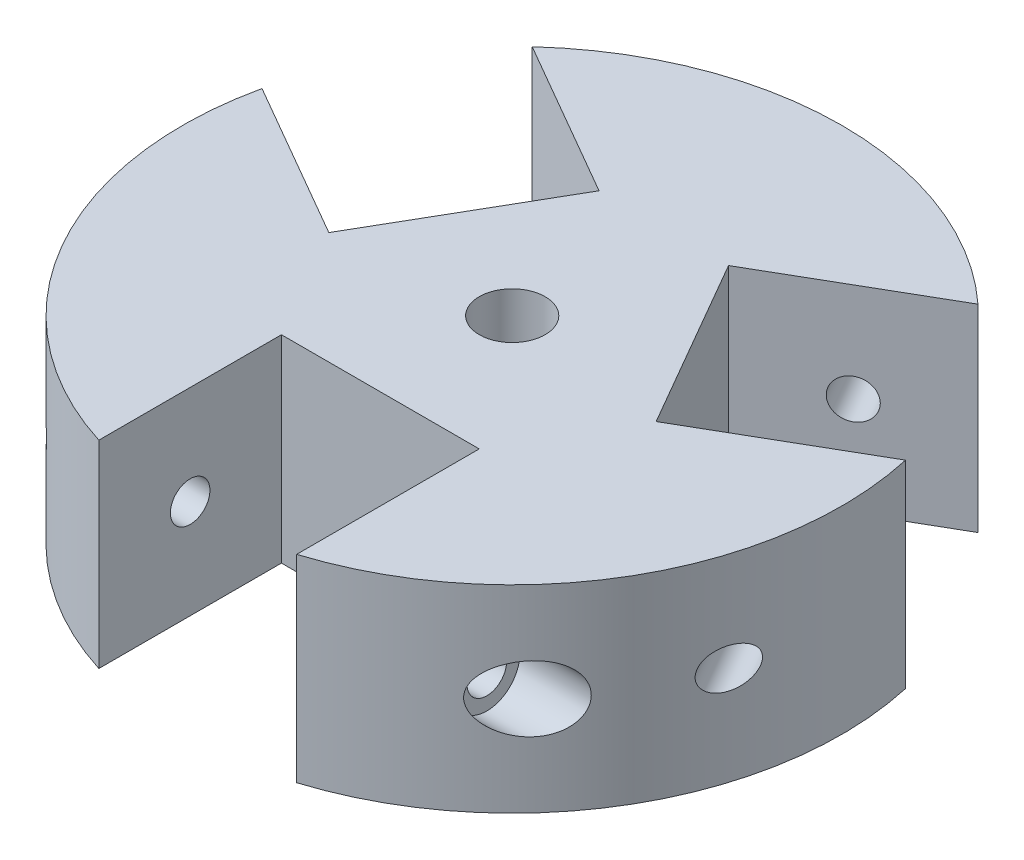
SolidWorks part; units mm, degrees
ref_plane "Front Plane" through (0, 0, 0) normal (0, 0, 1) x (1, 0, 0)
ref_plane "Top Plane" through (0, 0, 0) normal (0, 1, 0) x (1, 0, 0)
ref_plane "Right Plane" through (0, 0, 0) normal (1, 0, 0) x (0, 0, -1)
sketch "Sketch1" plane through (0, 0, 0) normal (0, 1, 0) x (1, 0, 0)
  circle A0 centre (0, 0) radius 25
  dimension "D1" = 50
extrude "Boss-Extrude1" add sketch "Sketch1" along normal blind 15
sketch "Sketch2" plane through (0, 15, 0) normal (0, 1, 0) x (1, 0, 0)
  line L0 (-22.9129, -10) -> (22.9129, -10)
  line L1 (0, 0) -> (0, -10) construction
  line L2 (-7.5, -10) -> (-7.5, -23.8485)
  line L3 (7.5, -10) -> (7.5, -23.8485)
  circle A0 centre (0, 0) radius 25 construction
  circle A1 centre (0, 0) radius 25
  circle M5 centre (0, 0) radius 25
  dimension "D1" = 7.5
  dimension "D2" = 7.5
  dimension "D3" = 10
extrude "Cut-Extrude1" cut sketch "Sketch2" against normal blind 150 contours L3 L0 L2 M5 region at (0, 15, 17.3139)
sketch "Sketch3" plane through (7.5, 0, 0) normal (-1, 0, 0) x (0, 0, 1)
  line L0 (16.9242, 7.5) -> (23.8485, 7.5) construction
  line L1 (16.9242, 7.5) -> (16.9242, 15) construction
  line L4 (23.8485, 15) -> (10, 15)
  line L5 (10, 15) -> (10, 0)
  line L6 (10, 0) -> (23.8485, 0)
  line L7 (23.8485, 0) -> (23.8485, 15)
  line L8 (23.8485, 15) -> (10, 15)
  line L9 (10, 15) -> (10, 0)
  line L10 (10, 0) -> (23.8485, 0)
  line L11 (23.8485, 0) -> (23.8485, 15)
  circle A0 centre (16.9242, 7.5) radius 1.5
  point P8 (169.2424, 85.47)
  point P9 (23.8485, 7.5)
  dimension "D2" = 3
  dimension "D1" = 0
extrude "Cut-Extrude2" cut sketch "Sketch3" against normal through all and the other way through all contours A0
sketch "Sketch4" plane through (7.5, 0, 0) normal (-1, 0, 0) x (0, 0, 1)
  circle A0 centre (16.9242, 7.5) radius 2.5
  dimension "D1" = 5
extrude "Cut-Extrude3" cut sketch "Sketch4" against normal blind 10 from offset 7.5 contours A0 offset against normal yes
mirror "Mirror1" [suppressed] about plane through (0, 0, 0) normal (1, 0, 0)
pattern_circular "CirPattern1" count 3 over 360 about axis through (0, 15, 0) along (0, 1, 0) of "Mirror1", "Cut-Extrude3", "Cut-Extrude2", "Cut-Extrude1"
sketch "Sketch5" plane through (0, 15, 0) normal (0, 1, 0) x (1, 0, 0)
  circle A0 centre (0, 0) radius 2.5
  dimension "D1" = 5
extrude "Cut-Extrude4" cut sketch "Sketch5" against normal through all
